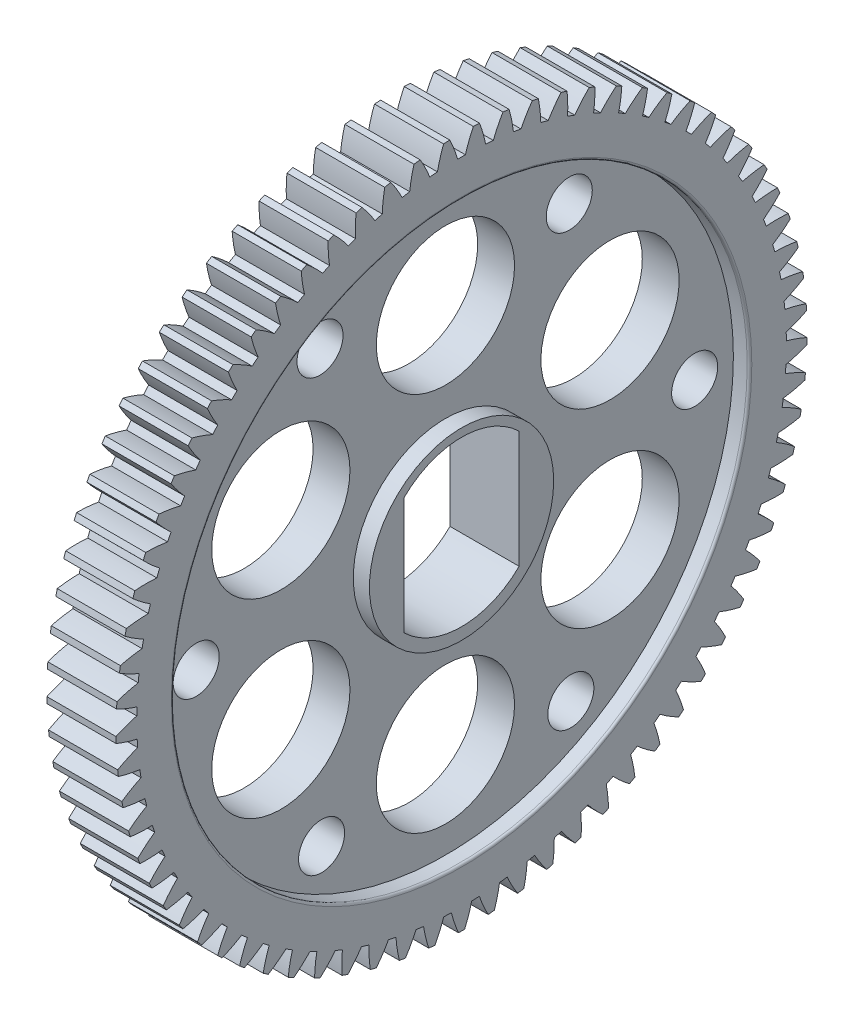
SolidWorks part; units mm, degrees
material "Alloy Steel"
ref_plane "Plane1" through (0, 0, 0) normal (0, 0, 1) x (1, 0, 0)
ref_plane "Plane2" through (0, 0, 0) normal (0, 1, 0) x (1, 0, 0)
ref_plane "Plane3" through (0, 0, 0) normal (1, 0, 0) x (0, 0, -1)
other "Configuration Table"
sketch "HoldingSke" plane through (0, 0, 0) normal (0, 1, 0) x (1, 0, 0)
  line L0 (0, 0) -> (0.1462, -0.4782)
  line L1 (-15, 0) -> (100, 0) construction
  line L2 (0, 0) -> (-2.1039, 2.3779)
  line L3 (0, 0) -> (-11.863, 4.5341)
  line L4 (0, 0) -> (2.5249, 8.2586)
  line L5 (0, 0) -> (-46.8476, -17.4728)
  line L6 (0, 0) -> (-12.4344, -8.3896)
  line L7 (-2.1039, 2.3779) -> (8.6586, 51.2059)
  line L8 (-76.2, 54.61) -> (-76.1, 54.61)
  line L9 (-71.009, 38.7566) -> (-53.1078, 45.2721)
  line L10 (-76.2, 71.12) -> (104.1128, 71.12)
  line L11 (0, 0) -> (-15, 0)
  line L12 (-76.2, 101.6) -> (-76.133, 101.6)
  line L13 (24.9733, 27.94) -> (52.9518, 28.4284)
  line L14 (24.9733, 27.94) -> (24.9743, 27.94)
  line L15 (24.9733, 27.94) -> (100.4006, 29.5858)
  line L16 (-63.627, -2) -> (-12.827, -2)
  circle A0 centre (0, 0) radius 0.4
  circle A1 centre (0, 0) radius 37.5
  circle A2 centre (0, 0) radius 37.5
  circle A3 centre (0, 0) radius 0.4
  dimension "MHD" = 75
  dimension "Hub_dia" = 75
  dimension "Bore" = 0.8
  dimension "MBD" = 0.8
  dimension "Num_teeth" = 73
  dimension "Pitch" = 0.5
  dimension "Overall_len" = 50
  dimension "Show_teeth" = 73
  dimension "Thickness" = 15
  dimension "OAL" = 50.0001
  dimension "T_dim" = 0.1
  dimension "Ap" = 20
  dimension "H" = 19.05
  dimension "Pitch_radius" = 180.3128
  dimension "Width" = 15
  dimension "Backlash" = 0.067
  dimension "Addendum_fac" = 1
  dimension "Dedendum_fac" = 1.25
  dimension "Clearance_fac" = 0.25
  dimension "Dedendum_add" = 0.001
  dimension "Module" = 2
sketch "BasProSke" plane through (0, 0, 0) normal (0, 1, 0) x (1, 0, 0)
  line L0 (-10, 0) -> (60, 0) construction
  line L1 (0, 0) -> (0, 75)
  line L2 (0, 0) -> (15, 0)
  line L3 (15, 0) -> (15, 75)
  line L4 (15, 75) -> (0, 75)
  dimension "Thickness" = 15
  dimension "Diameter" = 150
revolve "Base-Revolve" add sketch "BasProSke" angle 360 about L0
sketch "TooCutSke" plane through (0, 0, 0) normal (1, 0, 0) x (0, 0, -1)
  line L1 (0, 0) -> (0, 107) construction
  line L2 (0, 0) -> (-1.6879, 72.9805) construction
  line L3 (0, 0) -> (-6.28, 145.8359) construction
  line L4 (-1.6879, 72.9805) -> (-3.14, 72.918) construction
  arc A0 (0.8318, 70.4941) -> (-0.8318, 70.4941) centre (0, 0) ccw
  arc A1 (2.5674, 74.9815) -> (-2.5674, 74.9815) centre (0, 0) ccw
  circle A2 centre (0, 0) radius 73 construction
  circle A3 centre (0, 0) radius 68.5976 construction
  arc A4 (-0.8318, 70.4941) -> (-2.5674, 74.9815) centre (-28.8409, 62.2401) ccw
  arc A5 (2.5674, 74.9815) -> (0.8318, 70.4941) centre (28.8409, 62.2401) ccw
  dimension "Root_dia" = 140.998
  dimension "Overcut_dia" = 150.0508
  dimension "Pitch_dia" = 146
  dimension "Base_dia" = 137.1951
  dimension "Flank_rad" = 29.2
  dimension "Half_ang" = 2.466
  dimension "Half_CT" = 1.4534
extrude "ToothCut" cut sketch "TooCutSke" along normal through all
fillet "Breaks" [suppressed] radius 0.04 tangent propagation no
fillet "RootFillets" [suppressed] radius 0.501
pattern_circular "TeethCuts" count 73 every 4.932 about axis through (-10, 0, 0) along (1, 0, 0) of "ToothCut", "RootFillets", "Breaks"
sketch "HubNeaOneSke" plane through (0, 0, 0) normal (-1, 0, 0) x (0, 0, 1)
  circle A0 centre (0, 0) radius 37.5
  dimension "Diameter" = 75
extrude "HubNearOne" [suppressed] add sketch "HubNeaOneSke" along normal blind 35.0001
sketch "HubNeaBotSke" plane through (0, 0, 0) normal (-1, 0, 0) x (0, 0, 1)
  circle A0 centre (0, 0) radius 37.5
  dimension "Diameter" = 75
extrude "HubNearBoth" [suppressed] add sketch "HubNeaBotSke" along normal blind 17.5
ref_plane "FarPln" through (15, 0, 0) normal (1, 0, 0) x (0, 0, -1)
sketch "HubFarSke" plane through (15, 0, 0) normal (1, 0, 0) x (0, 0, -1)
  circle A0 centre (0, 0) radius 37.5
  dimension "Diameter" = 75
extrude "HubFar" [suppressed] add sketch "HubFarSke" along normal blind 17.5
sketch "BorSke" plane through (0, 0, 0) normal (1, 0, 0) x (0, 0, -1)
  circle A0 centre (0, 0) radius 0.4
  dimension "Diameter" = 0.8
extrude "Bore" cut sketch "BorSke" along normal mid plane 100.0001
sketch "KeySke" plane through (0, 0, 0) normal (1, 0, 0) x (0, 0, -1)
  line L0 (-0.05, 0) -> (-0.05, 0.5)
  line L1 (-0.05, 0.5) -> (0.05, 0.5)
  line L2 (0.05, 0.5) -> (0.05, 0)
  line L3 (0, 0) -> (0, 34) construction
  line L4 (-0.05, 0) -> (0.05, 0)
  dimension "Offset" = 0.5
  dimension "Width" = 0.1
extrude "Keyway" [suppressed] cut sketch "KeySke" along normal mid plane 100.0001
pattern_circular "Keyway2" [suppressed] count 2 every 90 about axis through (-10, 0, 0) along (1, 0, 0)
sketch "Sketch1" plane through (15, 0, 0) normal (1, 0, 0) x (0, 0, -1)
  circle A0 centre (0, 0) radius 62.5
extrude "Cut-Extrude1" cut sketch "Sketch1" against normal blind 3.5
extrude "Cut-Extrude2" cut sketch "Sketch1<2>" along normal blind 3.5 from surface starting at face at (0, 0, -0.4)
sketch "Sketch1<2>" plane through (15, 0, 0) normal (1, 0, 0) x (0, 0, -1) same geometry as "Sketch1"
fillet "Fillet1" radius 0.5 2 edges at (0, 0, -62.5) (15, 0, -62.5)
sketch "Sketch2" plane through (3.5, 0, 0) normal (-1, 0, 0) x (0, 0, 1)
  circle A0 centre (0, -0.4) radius 20
  circle A1 centre (0, 0) radius 0.4 construction
extrude "Boss-Extrude1" add sketch "Sketch2" along normal blind 3.5
extrude "Boss-Extrude2" add sketch "Sketch2<2>" against normal blind 3.5 from surface starting at face at (11.5, 0, -0.4)
sketch "Sketch2<2>" plane through (3.5, 0, 0) normal (-1, 0, 0) x (0, 0, 1) same geometry as "Sketch2"
sketch "Sketch3" plane through (15, 0, 0) normal (1, 0, 0) x (0, 0, -1)
  line L0 (0, 0) -> (0, 17.8177) construction
  line L1 (12.5, 12.6973) -> (12.5, -12.6973)
  line L2 (-12.5, 12.6973) -> (-12.5, -12.6973)
  arc A0 (-12.5, -12.6973) -> (12.5, -12.6973) centre (0, 0) ccw
  arc A1 (12.5, 12.6973) -> (-12.5, 12.6973) centre (0, 0) ccw
  dimension "D1" = 25
extrude "Cut-Extrude3" cut sketch "Sketch3" against normal up to next
sketch "Sketch4" plane through (11.5, 0, 0) normal (1, 0, 0) x (0, 0, -1)
  line L0 (26.8727, 46.5448) -> (0, 0) construction
  line L1 (0, 0) -> (89.6738, 0) construction
  circle A0 centre (0, -0.4) radius 41.25 construction
  circle A1 centre (0, 40.85) radius 15
  circle A2 centre (0, -0.4) radius 54.0921 construction
  circle A3 centre (26.8727, 46.5448) radius 5
  dimension "D1" = 60
extrude "Cut-Extrude4" cut sketch "Sketch4" against normal up to next
pattern_circular "CirPattern1" count 6 over 360 about axis through (15, -0.4, 0) along (-1, 0, 0) of "Cut-Extrude4"
equation "' \"Module@HoldingSke\" = 6.35"
equation "' \"Num_teeth@HoldingSke\" = 12"
equation "' \"Ap@HoldingSke\" =  20"
equation "' \"Ap@HoldingSke\" = 20"
equation "' \"Width@HoldingSke\" = 0.5 * 25.4"
equation "' \"Hub_dia@HoldingSke\"= 1 * 25.4"
equation "' \"Hub_dia@HoldingSke\" = 1 * 25.4"
equation "' \"Overall_len@HoldingSke\" = 1.0 * 25.4"
equation "' \"Bore@HoldingSke\" = 0.75 * 25.4"
equation "' \"T_dim@HoldingSke\" = 0.1 * 25.4"
equation "' \"Width@KeySke\" = 0.25 * 25.4"
equation "' \"Show_teeth@HoldingSke\" = 13"
equation "' \"Backlash@HoldingSke\" = 0.009 * 25.4"
equation "' \"Addendum_fac@HoldingSke\" = 1.0"
equation "' \"Dedendum_fac@HoldingSke\" = 1.25"
equation "' \"Dedendum_add@HoldingSke\" = 0.00005 * 25.4"
equation "' \"Clearance_fac@HoldingSke\" = 0.25"
equation "\"Pitch@HoldingSke\" = 1 / \"Module@HoldingSke\""
equation "\"Overcut_dia@TooCutSke\" = (\"Num_teeth@HoldingSke\" + 2 * \"Addendum_fac@HoldingSke\") / \"Pitch@HoldingSke\" + 0.002 * 25.4"
equation "\"Pitch_dia@TooCutSke\" = \"Num_teeth@HoldingSke\" / \"Pitch@HoldingSke\""
equation "\"Base_dia@TooCutSke\" = \"Num_teeth@HoldingSke\" / \"Pitch@HoldingSke\" * cos((\"Ap@HoldingSke\"  * 3.14159265 / 180))"
equation "\"Root_dia@TooCutSke\" = (\"Num_teeth@HoldingSke\" + 2) / \"Pitch@HoldingSke\" - 2 * (\"Addendum_fac@HoldingSke\" + \"Dedendum_fac@HoldingSke\") / \"Pitch@HoldingSke\" - \"Dedendum_add@HoldingSke\" * 2"
equation "\"Half_ang@TooCutSke\" = 180 / \"Num_teeth@HoldingSke\""
equation "\"Half_CT@TooCutSke\" = \"Num_teeth@HoldingSke\" / \"Pitch@HoldingSke\" * sin((3.14159265 / 2 / \"Num_teeth@HoldingSke\")) / 2 - 7 * \"Backlash@HoldingSke\" / 4"
equation "\"Flank_rad@TooCutSke\" = \"Num_teeth@HoldingSke\" / \"Pitch@HoldingSke\" / 5"
equation "\"Radius@RootFillets\" = \"Clearance_fac@HoldingSke\" / \"Pitch@HoldingSke\" + \"Dedendum_add@HoldingSke\""
equation "\"Break_rad@Breaks\" = 0.02 / \"Pitch@HoldingSke\""
equation "\"Thickness@HoldingSke\" = \"Width@HoldingSke\""
equation "\"OAL@HoldingSke\" = \"Thickness@HoldingSke\""
equation "\"MHD@HoldingSke\" = (\"Num_teeth@HoldingSke\" + 2) / \"Pitch@HoldingSke\" - 2 * (\"Addendum_fac@HoldingSke\" + \"Dedendum_fac@HoldingSke\")  / \"Pitch@HoldingSke\" - \"Dedendum_add@HoldingSke\" * 2"
equation "\"MBD@HoldingSke\" = (\"Num_teeth@HoldingSke\" + 2) / \"Pitch@HoldingSke\" - 2 * (\"Addendum_fac@HoldingSke\" + \"Dedendum_fac@HoldingSke\")  / \"Pitch@HoldingSke\" - \"Dedendum_add@HoldingSke\" * 2 - 0.002 * 25.4"
equation "\"MHD@HoldingSke\" = ((sgn( \"MHD@HoldingSke\" - \"Hub_dia@HoldingSke\" )-1)*( \"MHD@HoldingSke\" - \"Hub_dia@HoldingSke\" ))/-2+ \"Hub_dia@HoldingSke\""
equation "\"MBD@HoldingSke\" = ((sgn( \"MBD@HoldingSke\" - \"Bore@HoldingSke\" )-1)*( \"MBD@HoldingSke\" - \"Bore@HoldingSke\" ))/-2+ \"Bore@HoldingSke\""
equation "\"OAL@HoldingSke\" = ((sgn( \"OAL@HoldingSke\" - \"Overall_len@HoldingSke\" )+1)*( \"OAL@HoldingSke\" - \"Overall_len@HoldingSke\" ))/2 + \"Overall_len@HoldingSke\" + 0.000002 * 25.4"
equation "\"Num_teeth@TeethCuts\" = int( \"Show_teeth@HoldingSke\" ) + 1"
equation "\"Num_teeth@TeethCuts\" = ((sgn( \"Num_teeth@TeethCuts\" - \"Num_teeth@HoldingSke\" )-1)*( \"Num_teeth@TeethCuts\" - \"Num_teeth@HoldingSke\" ))/-2+ \"Num_teeth@HoldingSke\""
equation "\"Num_teeth@TeethCuts\" = ((sgn( \"Num_teeth@TeethCuts\" - 2.0)+1)*( \"Num_teeth@TeethCuts\" - 2.0))/2 +2.0"
equation "\"Angle@TeethCuts\" = 360.0 / \"Num_teeth@HoldingSke\""
equation "\"Diameter@BasProSke\" = (\"Num_teeth@HoldingSke\" + 2 * \"Addendum_fac@HoldingSke\") / \"Pitch@HoldingSke\""
equation "\"Thickness@BasProSke\"  = \"Thickness@HoldingSke\""
equation "' \"Fillet_rad@BasProSke\" =  \"Thickness@HoldingSke\" * 0.05"
equation "' \"Fillet_rad@BasProSke\" = \"Thickness@HoldingSke\" * 0.05"
equation "\"MHD@HoldingSke\" = ((sgn( \"MHD@HoldingSke\" - \"Root_dia@TooCutSke\" )-1)*( \"MHD@HoldingSke\" - \"Root_dia@TooCutSke\" ))/-2+ \"Root_dia@TooCutSke\""
equation "\"Diameter@HubNeaOneSke\" = \"MHD@HoldingSke\""
equation "\"Length@HubNearOne\" = \"OAL@HoldingSke\" - \"Thickness@BasProSke\""
equation "\"Diameter@HubNeaBotSke\" = \"MHD@HoldingSke\""
equation "\"Length@HubNearBoth\" = ( \"OAL@HoldingSke\" - \"Thickness@BasProSke\" ) / 2.0"
equation "\"Thickness@FarPln\" = \"Thickness@BasProSke\""
equation "\"Diameter@HubFarSke\" = \"MHD@HoldingSke\""
equation "\"Length@HubFar\" = ( \"OAL@HoldingSke\" - \"Thickness@BasProSke\" ) / 2.0"
equation "\"Diameter@BorSke\" = \"MBD@HoldingSke\""
equation "\"D1@Bore\" = \"OAL@HoldingSke\" * 2.0"
equation "\"D1@Keyway\" = \"OAL@HoldingSke\" * 2.0"
equation "\"Offset@KeySke\" = \"T_dim@HoldingSke\" + \"MBD@HoldingSke\" / 2.0"
